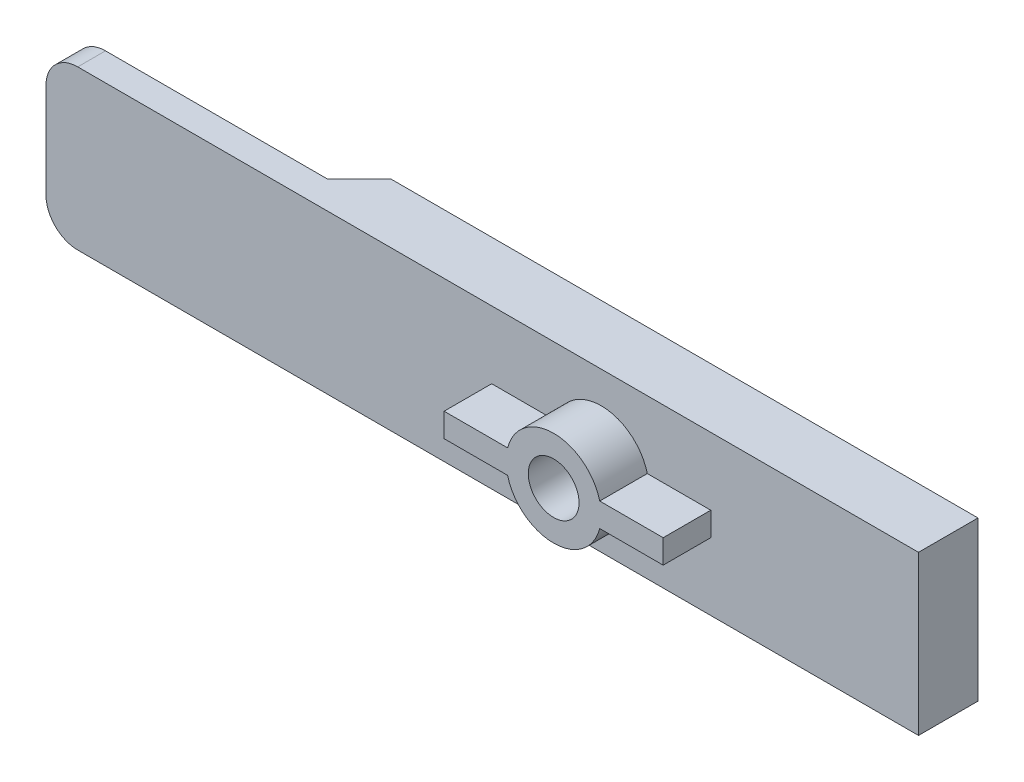
SolidWorks part; units mm, degrees
ref_plane "前视基准面" through (0, 0, 0) normal (0, 0, 1) x (1, 0, 0)
ref_plane "上视基准面" through (0, 0, 0) normal (0, 1, 0) x (1, 0, 0)
ref_plane "右视基准面" through (0, 0, 0) normal (1, 0, 0) x (0, 0, -1)
sketch "草图1" plane through (0, 0, 0) normal (0, 0, 1) x (1, 0, 0)
  line L1 (0, 0) -> (40, 0)
  line L2 (0, 0) -> (0, 10)
  line L3 (0, 10) -> (40, 10)
  line L4 (40, 0) -> (40, 10)
  line L5 (0, 0) -> (40, 10) construction
  line L6 (0, 10) -> (40, 0) construction
  point P4 (20, 5)
  dimension "D1" = 40
  dimension "D2" = 10
extrude "凸台-拉伸1" add sketch "草图1" along normal blind 1.75
sketch "草图2" plane through (0, 0, 1.75) normal (0, 0, 1) x (1, 0, 0)
  line L0 (40, 10) -> (0, 10) construction
  line L1 (17.5, 10) -> (22.5, 10)
  line L2 (17.5, 10) -> (17.5, 0)
  line L3 (17.5, 0) -> (22.5, 0)
  line L4 (22.5, 10) -> (22.5, 0)
  line L5 (17.5, 10) -> (22.5, 0) construction
  line L6 (17.5, 0) -> (22.5, 10) construction
  line L7 (0, 0) -> (40, 0) construction
  line L8 (20, 10) -> (20, 0) construction
  point P4 (20, 5)
  dimension "D1" = 5
sketch "草图3" plane through (0, 0, 0) normal (0, 0, -1) x (-1, 0, 0)
  line L0 (0, 0) -> (-40, 0) construction
  line L1 (-40, 10) -> (-36, 10)
  line L2 (-40, 10) -> (-40, 0)
  line L3 (-40, 0) -> (-36, 0)
  line L4 (-36, 10) -> (-36, 0)
  line L5 (-40, 10) -> (-36, 0) construction
  line L6 (-40, 0) -> (-36, 10) construction
  point P4 (-38, 5)
  dimension "D1" = 4
extrude "凸台-拉伸3" add sketch "草图3" along normal blind 2
sketch "草图4" plane through (0, 0, 0) normal (0, 0, -1) x (-1, 0, 0)
  line L0 (-36, 0) -> (-36, 10) construction
  line L1 (-36, 6.5) -> (0, 6.5)
  line L2 (-36, 6.5) -> (-36, 3.5)
  line L3 (-36, 3.5) -> (0, 3.5)
  line L4 (0, 6.5) -> (0, 3.5)
  line L5 (0, 10) -> (0, 0) construction
  line L6 (-36, 5) -> (0, 5) construction
  line L7 (-36, 0) -> (-36, 10) construction
  line L8 (0, 0) -> (-36, 0) construction
  line L9 (0, 10) -> (-3, 10)
  line L10 (0, 10) -> (0, 0)
  line L11 (0, 0) -> (-3, 0)
  line L12 (-3, 10) -> (-3, 0)
  line L13 (-36, 10) -> (0, 10) construction
  line L14 (-21, 10) -> (-18, 10)
  line L15 (-21, 10) -> (-21, 0)
  line L16 (-21, 0) -> (-18, 0)
  line L17 (-18, 10) -> (-18, 0)
  line M6 (-36, 10) -> (-36, 0)
  line M7 (-36, 0) -> (0, 0)
  line M8 (0, 0) -> (0, 10)
  line M9 (0, 10) -> (-36, 10)
  dimension "D1" = 3
  dimension "D2" = 3
  dimension "D3" = 3
  dimension "D4" = 18
extrude "凸台-拉伸4" add sketch "草图4" along normal up to surface (2 mm away) contours L6 L15 L1 M6 | L6 L2 L3 L15 | L15 L6 L17 L1 | L6 L15 L3 L17 | L17 L15 L1 M9 | L17 L3 L15 M7 | L17 L6 L12 L1 | L6 L17 L3 L12 | L12 L6 L10 L1 | L6 L12 L3 M8 | L12 L1 M9 M8 | L3 L12 M7 M8 region at (28.5, 5.75, 0) region at (19.5, 8.25, 0) region at (19.5, 5.75, 0) region at (28.5, 4.25, 0) region at (10.5, 5.75, 0) region at (19.5, 4.25, 0) region at (1.5, 8.25, 0) region at (1.5, 5.75, 0) region at (10.5, 4.25, 0) region at (19.5, 1.75, 0) region at (1.5, 4.25, 0) region at (1.5, 1.75, 0) up to face at (38, 5, -2)
chamfer "倒角1" distance 1 angle 45 4 edges at (10.5, 3.5, -2) (28.5, 3.5, -2) (10.5, 3.5, 0) (28.5, 3.5, 0)
sketch "草图6" plane through (0, 0, 1.75) normal (0, 0, 1) x (1, 0, 0)
  line L0 (0, 5) -> (40, 5) construction
  line L1 (0, 10) -> (0, 0) construction
  line L3 (40, 0) -> (40, 10) construction
  circle A0 centre (20, 5) radius 1.6
  circle A2 centre (20, 5) radius 3
  dimension "D1" = 3.2
  dimension "D3" = 6
extrude "凸台-拉伸5" add sketch "草图6" along normal blind 3
sketch "草图7" plane through (0, 0, 0) normal (-1, 0, 0) x (0, 0, 1)
  line L1 (0, 0) -> (1.75, 0)
  line L2 (0, 0) -> (0, 10)
  line L3 (0, 10) -> (1.75, 10)
  line L4 (1.75, 0) -> (1.75, 10)
extrude "凸台-拉伸6" add sketch "草图7" along normal blind 10
sketch "草图8" plane through (0, 0, 1.75) normal (0, 0, 1) x (1, 0, 0)
  line L0 (20, 8) -> (20, 2) construction
  line L1 (17.0953, 5.75) -> (13.0953, 5.75)
  line L2 (17.0953, 5.75) -> (17.0953, 4.25)
  line L3 (17.0953, 4.25) -> (13.0953, 4.25)
  line L4 (13.0953, 5.75) -> (13.0953, 4.25)
  line L5 (26.9047, 5.75) -> (26.9047, 4.25)
  line L6 (22.9047, 4.25) -> (26.9047, 4.25)
  line L7 (22.9047, 5.75) -> (22.9047, 4.25)
  line L8 (22.9047, 5.75) -> (26.9047, 5.75)
  circle A0 centre (20, 5) radius 3 construction
  circle A1 centre (20, 5) radius 3 construction
  dimension "D1" = 4
  dimension "D2" = 1.5
extrude "凸台-拉伸7" add sketch "草图8" along normal up to surface (3 mm away) up to face at (23, 5, 4.75)
sketch "草图9" plane through (0, 0, 0) normal (0, 0, -1) x (-1, 0, 0)
  line L1 (-3, 0) -> (-36, 0)
  line L2 (-3, 0) -> (-3, 10)
  line L3 (-3, 10) -> (-36, 10)
  line L4 (-36, 0) -> (-36, 10)
extrude "凸台-拉伸8" add sketch "草图9" along normal up to surface (2 mm away) up to face at (19.6, 5.2, -2)
chamfer "倒角2" distance 3 angle 45 1 edges at (0, 5, -2)
sketch "草图10" plane through (-10, 0, 0) normal (-1, 0, 0) x (0, 0, 1)
  line L4 (0, 10) -> (0, 0)
  line L5 (0, 0) -> (1.75, 0)
  line L6 (1.75, 0) -> (1.75, 10)
  line L7 (1.75, 10) -> (0, 10)
  line L8 (0, 10) -> (0, 0)
  line L9 (0, 0) -> (1.75, 0)
  line L10 (1.75, 0) -> (1.75, 10)
  line L11 (1.75, 10) -> (0, 10)
  dimension "D1" = 0
extrude "凸台-拉伸9" add sketch "草图10" along normal blind 5
fillet "圆角1" radius 2 2 edges at (-15, 0, 0.875) (-15, 10, 0.875)
sketch "草图11" plane through (0, 0, 1.75) normal (0, 0, 1) x (1, 0, 0)
  circle A1 centre (20, 5) radius 1.6
  circle A2 centre (20, 5) radius 1.6
  dimension "D1" = 0
extrude "切除-拉伸1" cut sketch "草图11" against normal offset from surface (1.75 mm away) 2 up to face at (21.5, 5, -2)
sketch "草图12" plane through (0, 0, 0) normal (0, 0, -1) x (-1, 0, 0)
  line L0 (-3, 5) -> (15, 5) construction
  line L1 (-3, 0) -> (-3, 10) construction
  line L2 (15, 8) -> (15, 2) construction
  line L4 (15, 6) -> (-3, 6)
  line L5 (15, 6) -> (15, 4)
  line L6 (15, 4) -> (-3, 4)
  line L7 (-3, 6) -> (-3, 4)
  dimension "D1" = 2
extrude "凸台-拉伸10" add sketch "草图12" along normal up to surface (2 mm away) up to face at (21.5, 5, -2)
sketch "草图13" plane through (0, 0, -2) normal (0, 0, -1) x (-1, 0, 0)
  line L8 (-40, 0) -> (-3, 0)
  line L9 (-3, 0) -> (-3, 4)
  line L10 (-3, 4) -> (15, 4)
  line L11 (15, 4) -> (15, 6)
  line L12 (15, 6) -> (-3, 6)
  line L13 (-3, 6) -> (-3, 10)
  line L14 (-3, 10) -> (-40, 10)
  line L15 (-40, 10) -> (-40, 0)
  line L16 (-40, 0) -> (-3, 0)
  line L17 (-3, 0) -> (-3, 4)
  line L18 (-3, 4) -> (15, 4)
  line L19 (15, 4) -> (15, 6)
  line L20 (15, 6) -> (-3, 6)
  line L21 (-3, 6) -> (-3, 10)
  line L22 (-3, 10) -> (-40, 10)
  line L23 (-40, 10) -> (-40, 0)
  dimension "D1" = 0
